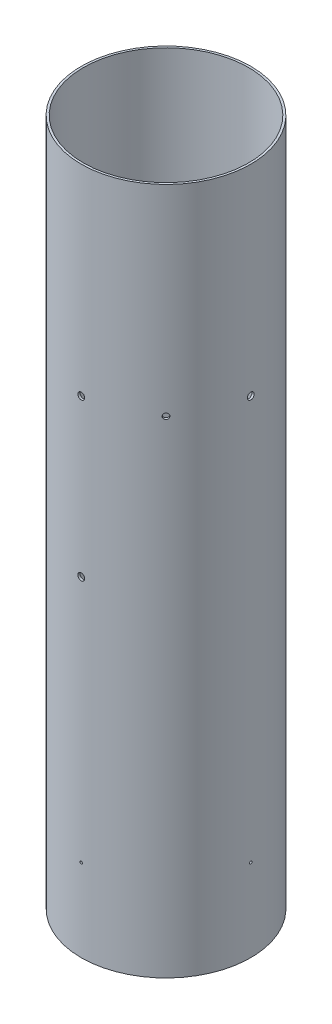
SolidWorks part; units mm, degrees
material "C-Glass Fiber"
ref_plane "Front Plane" through (0, 0, 0) normal (0, 0, 1) x (1, 0, 0)
ref_plane "Top Plane" through (0, 0, 0) normal (0, 1, 0) x (1, 0, 0)
ref_plane "Right Plane" through (0, 0, 0) normal (1, 0, 0) x (0, 0, -1)
sketch "Sketch2" plane through (0, 0, 0) normal (0, 1, 0) x (1, 0, 0)
  circle A0 centre (0, 0) radius 76.3651
  circle A1 centre (0, 0) radius 78.359
  dimension "D1" = 152.7302
  dimension "D2" = 156.718
extrude "Boss-Extrude1" add sketch "Sketch2" along normal blind 635
sketch "Sketch3" plane through (0, 0, 0) normal (0, 0, 1) x (1, 0, 0)
  circle A0 centre (0, 76.2) radius 1.1906
  dimension "D2" = 2.3813
  dimension "D1" = 76.2
extrude "Cut-Extrude1" cut sketch "Sketch3" against normal through all both and the other way through all
pattern_circular "CirPattern1" count 4 over 360 about axis through (0, 635, 0) along (0, 1, 0) of "Cut-Extrude1"
sketch "Sketch4" plane through (0, 0, 0) normal (0, 0, 1) x (1, 0, 0)
  circle A0 centre (0, 449.5038) radius 3.175
  dimension "D2" = 6.35
  dimension "D1" = 449.5038
extrude "Cut-Extrude2" cut sketch "Sketch4" against normal through all both and the other way through all
pattern_circular "CirPattern2" count 4 over 360 about axis through (0, 635, 0) along (0, 1, 0) of "Cut-Extrude2"
ref_plane "Plane1" through (55.4082, 0, 55.4082) normal (0.7071, 0, 0.7071) x (0, -1, 0)
sketch "Sketch5" plane through (55.4082, 0, 55.4082) normal (0.7071, 0, 0.7071) x (0, -1, 0)
  circle A0 centre (-449.5038, 0) radius 2.5794
  dimension "D1" = 5.1587
  dimension "D2" = 449.5038
extrude "Cut-Extrude3" cut sketch "Sketch5" against normal up to surface and the other way through all up to face at (-76.3025, 448.7766, 3.0906)
sketch "Sketch6" plane through (0, 0, 0) normal (0, 0, 1) x (1, 0, 0)
  circle A0 centre (0, 304.8) radius 3.175
  dimension "D2" = 304.8
extrude "Cut-Extrude4" cut sketch "Sketch6" against normal through all both and the other way through all
sketch "Sketch7" plane through (0, 635, 0) normal (0, 1, 0) x (1, 0, 0)
  line L0 (0, 0) -> (78.359, 0)
  circle A0 centre (0, 0) radius 78.359 construction
ref_plane "Plane2" through (0, 449.58, 0) normal (0, 1, 0) x (1, 0, 0)
sketch "Sketch8" plane through (0, 449.58, 0) normal (0, 1, 0) x (1, 0, 0)
  line L0 (0, 0) -> (78.359, 0) construction
  line L1 (0, 0) -> (78.359, 0) construction
  line L2 (0, 0) -> (53.8815, -53.8815) construction
  line L3 (0, 0) -> (0, 76.3651) construction
  line L4 (0, 0) -> (0, -76.3651) construction
  line L5 (0, 0) -> (-76.3651, 0) construction
  circle A0 centre (0, 0) radius 76.3651 construction
  dimension "D1" = 76.2
  dimension "D2" = 45
ref_plane "Plane3" through (0, 304.8, 0) normal (0, 1, 0) x (1, 0, 0)
sketch "Sketch9" plane through (0, 304.8, 0) normal (0, 1, 0) x (1, 0, 0)
  line L2 (0, 0) -> (0, 76.3651) construction
  line L3 (0, 0) -> (0, -76.3651) construction
  circle A0 centre (0, 0) radius 76.3651 construction
ref_plane "Plane4" through (0, 76.2, 0) normal (0, 1, 0) x (1, 0, 0)
sketch "Sketch10" plane through (0, 76.2, 0) normal (0, 1, 0) x (1, 0, 0)
  line L0 (0, 0) -> (78.359, 0) construction
  line L1 (0, 0) -> (0, 76.3651) construction
  line L2 (0, 0) -> (78.359, 0) construction
  line L3 (0, 0) -> (0, 76.3651) construction
  line L4 (0, 0) -> (-76.3651, 0) construction
  line L5 (0, 0) -> (0, -76.3651) construction
equation "\"Shear Pin Dia\"= 3 / 32"
equation "\"Shear Pin Offset\"= 3"
equation "\"D1@Sketch3\"=\"Shear Pin Offset\""
equation "\"D2@Sketch3\"=\"Shear Pin Dia\""
equation "\"Bulkhead Screw Dia\"= 1 / 4"
equation "\"Bulkhead Screw Offset\"= 17.697"
equation "\"D1@Sketch4\"=\"Bulkhead Screw Offset\""
equation "\"D2@Sketch4\"=\"Bulkhead Screw Dia\""
equation "\"Rail Button Offset\"= 17.697"
equation "\"Rail Button Dia\"=0.2031"
equation "\"D1@Sketch5\"=\"Rail Button Dia\""
equation "\"Vent Hole Dia\"= 0.25"
equation "\"Vent Hole Offset\"= 12"
equation "\"D2@Sketch6\"=\"Vent Hole Offset\""
